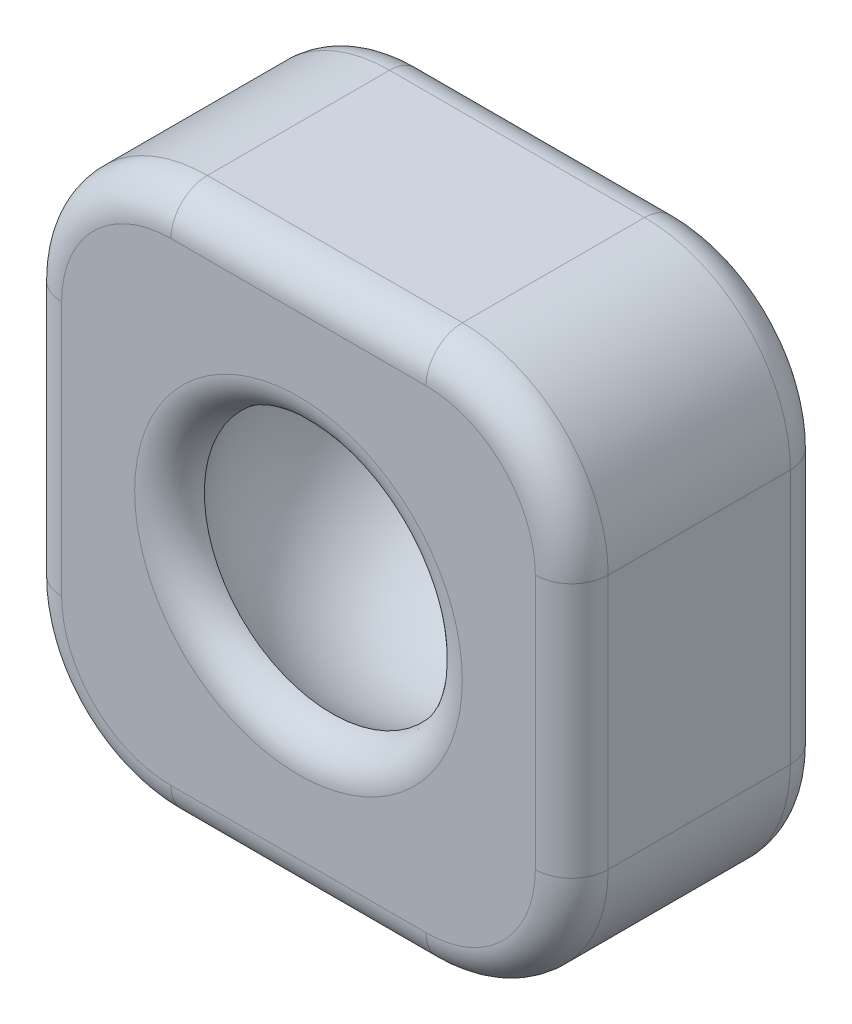
SolidWorks part; units mm, degrees
material "PLA_Rotula_Chica"
ref_plane "Front Plane" through (0, 0, 0) normal (0, 0, 1) x (1, 0, 0)
ref_plane "Top Plane" through (0, 0, 0) normal (0, 1, 0) x (1, 0, 0)
ref_plane "Right Plane" through (0, 0, 0) normal (1, 0, 0) x (0, 0, -1)
ref_plane "Plane1" through (0, 0, 5) normal (0, 0, 1) x (1, 0, 0)
sketch "Sketch1" plane through (0, 0, 5) normal (0, 0, 1) x (1, 0, 0)
  line L0 (-7.5, -7.5) -> (7.5, -7.5)
  line L1 (7.5, -7.5) -> (7.5, 7.5)
  line L2 (7.5, 7.5) -> (-7.5, 7.5)
  line L3 (-7.5, 7.5) -> (-7.5, -7.5)
  line L4 (-7.5, 7.5) -> (7.5, -7.5) construction
  line L5 (7.5, 7.5) -> (-7.5, -7.5) construction
  circle A0 centre (0, 0) radius 3.5
  dimension "D3" = 7
  dimension "D1" = 15
  dimension "D2" = 15
extrude "Boss-Extrude1" add sketch "Sketch1" against normal blind 3.5 and the other way blind 3.5
sketch "Sketch2" plane through (0, 0, 0) normal (0, 1, 0) x (1, 0, 0)
  line L0 (3.5, -2.4169) -> (3.5, -7.5831)
  line L1 (0, -1.5) -> (0, -8.5) construction
  line L2 (-55, -5) -> (55, -5) construction
  line L3 (3.5, -1.5) -> (-3.5, -1.5) construction
  line L4 (-3.5, -8.5) -> (3.5, -8.5) construction
  arc A0 (3.5, -7.5831) -> (3.5, -2.4169) centre (0, -5) ccw
  dimension "D1" = 4.35
  dimension "D2" = 3.5
revolve "Cut-Revolve1" cut sketch "Sketch2" angle 360 about L1 reverse direction yes
fillet "Fillet1" radius 4 4 edges at (-7.5, 7.5, 5) (-7.5, -7.5, 5) (7.5, 7.5, 5) (7.5, -7.5, 5) tangent propagation no
fillet "Fillet2" radius 1 18 edges at (-3.5, 0, 8.5) (-6.3284, -6.3284, 8.5) (-7.5, 0, 8.5) (-6.3284, 6.3284, 8.5) (0, 7.5, 8.5) (6.3284, 6.3284, 8.5) (7.5, 0, 8.5) (6.3284, -6.3284, 8.5) (0, -7.5, 8.5) (6.3284, 6.3284, 1.5) (0, 7.5, 1.5) (-6.3284, 6.3284, 1.5) (-7.5, 0, 1.5) (-6.3284, -6.3284, 1.5) (0, -7.5, 1.5) (6.3284, -6.3284, 1.5) (7.5, 0, 1.5) (-3.5, 0, 1.5)
